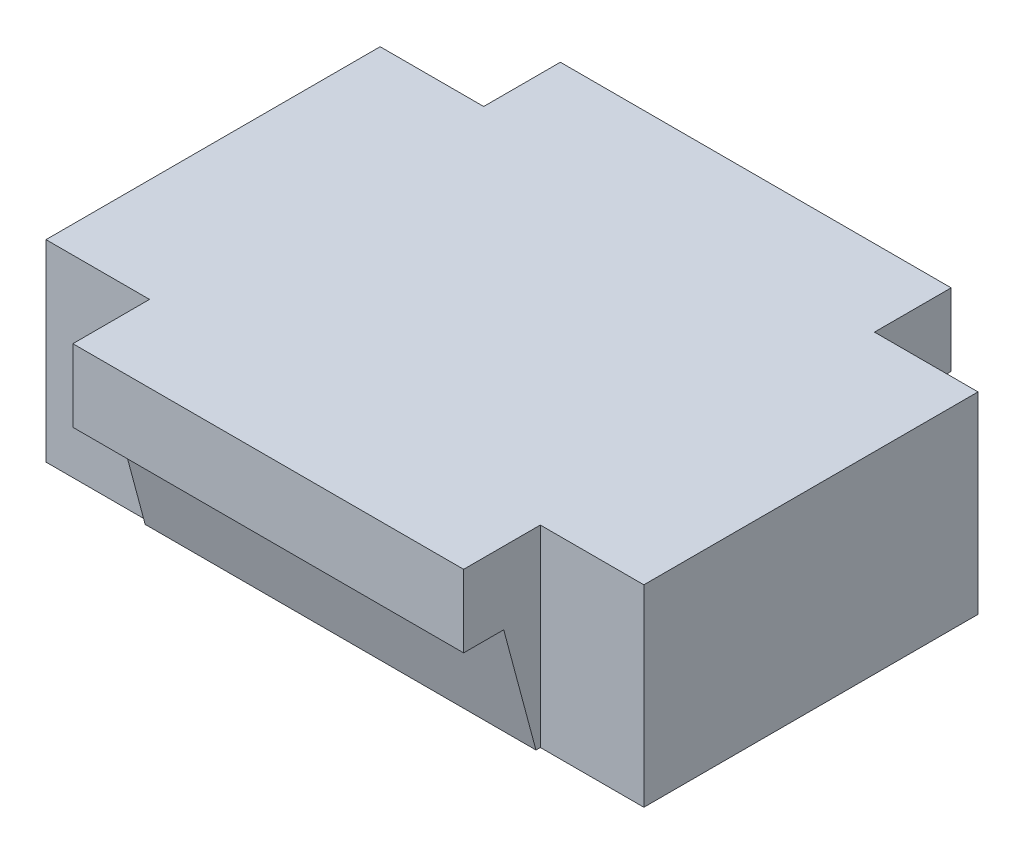
SolidWorks part; units mm, degrees
material "1060 Alloy"
ref_plane "Front Plane" through (0, 0, 0) normal (0, 0, 1) x (1, 0, 0)
ref_plane "Top Plane" through (0, 0, 0) normal (0, 1, 0) x (1, 0, 0)
ref_plane "Right Plane" through (0, 0, 0) normal (1, 0, 0) x (0, 0, -1)
sketch "Sketch2" plane through (0, 0, 0) normal (1, 0, 0) x (0, 0, -1)
  line L0 (0, 22.5899) -> (0, 0.5499) construction
  line L1 (-9.6464, -1.0186) -> (-9.6464, -2.6614) construction
  line L2 (-9.6464, -2.6614) -> (-8.0036, -2.6614) construction
  line L3 (-10, 0) -> (0, 0) construction
  line L4 (20.2658, -14.5) -> (-12.926, -14.5) construction
  line L8 (-8.235, -8.9) -> (-20.12, -8.9)
  line L9 (-20.12, -8.9) -> (-21.59, -7.43)
  line L10 (-21.59, -7.43) -> (-21.59, 14.03)
  line L11 (-21.59, 14.03) -> (-20.12, 15.5)
  line L12 (-20.12, 15.5) -> (0, 15.5)
  line L13 (-20.12, 15.5) -> (-20.12, -8.9) construction
  line L14 (0, 15.5) -> (0, 3.015)
  line L17 (-6.5, -7.165) -> (-8.235, -8.9)
  line L18 (-6.5, -4.165) -> (-6.5, -7.165)
  line L19 (-8.0036, -2.6614) -> (-6.5, -4.165)
  line L20 (-10, -0.665) -> (-9.6464, -1.0186)
  line L21 (-10, 0.665) -> (-10, -0.665)
  line L22 (-9.6464, 1.0186) -> (-10, 0.665)
  line L23 (-7.65, 3.015) -> (-8.0036, 2.6614)
  line L24 (0, 3.015) -> (-7.65, 3.015)
  line L25 (-8.0036, 2.6614) -> (-9.6464, 1.0186) construction
  line L26 (-9.6464, -1.0186) -> (-8.0036, -2.6614) construction
  line L27 (-8.0036, 2.6614) -> (-9.6464, 2.6614) construction
  line L28 (-9.6464, 2.6614) -> (-9.6464, 1.0186) construction
  arc A2 (-8.0036, -2.6614) -> (-9.6464, -1.0186) centre (-9.6464, -2.6614) ccw
  arc A3 (-9.6464, 1.0186) -> (-8.0036, 2.6614) centre (-9.6464, 2.6614) ccw
  point P4 (-10, 0)
  point P5 (-23.309, 31.262)
  dimension "D2" = 0.5
  dimension "D3" = 10
  dimension "D4" = 45
  dimension "D5" = 1.33
  dimension "D6" = 30
  dimension "D7" = 7.65
  dimension "D8" = 3
  dimension "D9" = 21.59
  dimension "D10" = 1.47
  dimension "D11" = 21.46
  dimension "D12" = 45
  dimension "D13" = 6.5
  dimension "D14" = 24.4
  dimension "D15" = 14.5
extrude "Boss-Extrude1" add sketch "Sketch2" along normal blind 38.63
sketch "Sketch3" plane through (0, 0, 0) normal (1, 0, 0) x (0, 0, -1)
  line L0 (-20.12, -8.9) -> (-21.12, -8.9)
  line L1 (-21.12, -8.9) -> (-22.5342, -7.4858)
  line L2 (-22.5342, -7.4858) -> (-26.3203, 6.6442)
  line L3 (-26.3203, 6.6442) -> (-31.5, 6.6442)
  line L4 (-31.5, 6.6442) -> (-31.5, 16)
  line L5 (-31.5, 16) -> (-20.855, 16)
  line L6 (-20.855, 16) -> (-20.855, 15.6)
  line L7 (-20.855, 15.6) -> (-5.355, 15.6)
  line L8 (-5.355, 15.6) -> (-5.355, 16)
  line L9 (-5.355, 16) -> (0, 16)
  line L10 (0, 16) -> (0, 15.5)
  line L11 (0, 15.5) -> (-20.12, 15.5)
  line L12 (-20.12, 15.5) -> (-21.59, 14.03)
  line L13 (-21.59, 14.03) -> (-21.59, -7.43)
  line L14 (-21.59, -7.43) -> (-20.12, -8.9)
  line L15 (-22.5342, -7.4858) -> (-30.0907, -7.4858) construction
  line L16 (-20.855, 15.6) -> (-20.855, 14.765) construction
  line L17 (-20.855, 16) -> (-5.355, 16) construction
  line L18 (0, 3.015) -> (0, 15.5) construction
  dimension "D1" = 1
  dimension "D2" = 45
  dimension "D3" = 2
  dimension "D4" = 75
  dimension "D5" = 14.13
  dimension "D6" = 31.5
  dimension "D7" = 0.5
  dimension "D8" = 0.1
  dimension "D9" = 15.5
extrude "Boss-Extrude2" add sketch "Sketch3" along normal offset from surface (25.25 mm away) 13.38 up to face at (38.63, 0.9063, 10.4328)
chamfer "Chamfer1" [suppressed] distance 1 angle 45
sketch "Sketch4" [suppressed] plane through (0, 16, 0) normal (0, 1, 0) x (1, 0, 0)
  line L0 (20, -26.5) -> (25.25, -26.5) construction
  line L1 (25.25, -20.855) -> (25.25, -30.5) construction
  line L2 (20, -26.5) -> (20, -31.5) construction
  line L3 (25.25, -31.5) -> (0, -31.5) construction
  line L4 (25.25, 0) -> (0, 0) construction
  circle A0 centre (20, -26.5) radius 2.45
  dimension "D1" = 4.9
  dimension "D2" = 26.5
  dimension "D3" = 5.25
extrude "Cut-Extrude1" [suppressed] cut sketch "Sketch4" against normal through all
sketch "Sketch5" [suppressed] plane through (0, 16, 0) normal (0, 1, 0) x (1, 0, 0)
  circle A0 centre (20, -26.5) radius 3
  dimension "D1" = 6
extrude "Cut-Extrude2" [suppressed] cut sketch "Sketch5" against normal through all from offset 8.5 offset against normal yes
mirror "Mirror1" about plane through (0, 0, 0) normal (0, 0, 1) of bodies 102 110
sketch "Sketch12" plane through (38.63, 0, 0) normal (1, 0, 0) x (0, 0, -1)
  line L0 (0, 10.5) -> (0, 0) construction
  line L1 (-20.12, 15.5) -> (20.12, 15.5) construction
  circle A0 centre (0, 10.5) radius 3.6
  dimension "D1" = 7.2
  dimension "D2" = 5
extrude "Cut-Extrude8" [suppressed] cut sketch "Sketch12" against normal blind 2.9
mirror "Mirror2" about plane through (0, 0, 0) normal (1, 0, 0) of bodies 111 113
sketch "Sketch13" plane through (38.63, 0, 0) normal (1, 0, 0) x (0, 0, -1)
  line L0 (20.12, -8.9) -> (8.235, -8.9) construction
  line L1 (-13.2605, 8.9173) -> (13.4108, 8.9173)
  line L2 (-13.2605, 8.9173) -> (-13.2605, -8.9)
  line L3 (-13.2605, -8.9) -> (13.4108, -8.9)
  line L4 (13.4108, 8.9173) -> (13.4108, -8.9)
extrude "Boss-Extrude3" add sketch "Sketch13" against normal up to surface (77.26 mm away) up to face at (-38.63, -0.2868, 0)
sketch "Sketch14" plane through (25.25, 0, 0) normal (1, 0, 0) x (0, 0, -1)
  line L0 (-31.5, 16) -> (31.5, 16)
  line L1 (31.5, 16) -> (31.5, 6.6442)
  line L2 (31.5, 6.6442) -> (26.3203, 6.6442)
  line L3 (26.3203, 6.6442) -> (22.1553, -8.9)
  line L4 (22.1553, -8.9) -> (-22.1553, -8.9)
  line L5 (-22.1553, -8.9) -> (-26.3203, 6.6442)
  line L6 (-26.3203, 6.6442) -> (-31.5, 6.6442)
  line L7 (-31.5, 6.6442) -> (-31.5, 16)
  line L8 (26.3203, 6.6442) -> (22.5342, -7.4858) construction
  line L9 (-20.12, -8.9) -> (20.12, -8.9) construction
  line L10 (-26.3203, 6.6442) -> (-22.5342, -7.4858) construction
  point P4 (24.0854, -9.7857)
extrude "Boss-Extrude4" add sketch "Sketch14" against normal up to surface (50.5 mm away) up to face at (-25.25, 6.8694, 0)
sketch "Sketch15" plane through (38.63, 0, 0) normal (1, 0, 0) x (0, 0, -1)
  line L0 (31.5, 16) -> (-31.5, 16) construction
  line L1 (-21.59, 16) -> (21.59, 16)
  line L2 (-21.59, 16) -> (-21.59, -8.9)
  line L3 (-21.59, -8.9) -> (21.59, -8.9)
  line L4 (21.59, 16) -> (21.59, -8.9)
  line L5 (-21.59, 14.03) -> (-21.59, -7.43) construction
  line L6 (21.59, -7.43) -> (21.59, 14.03) construction
  point P7 (0, 0)
  point P9 (0, 0)
  point P12 (0, 0)
extrude "Boss-Extrude5" add sketch "Sketch15" against normal up to surface (77.26 mm away) up to face at (-38.63, 3.3, 0)
